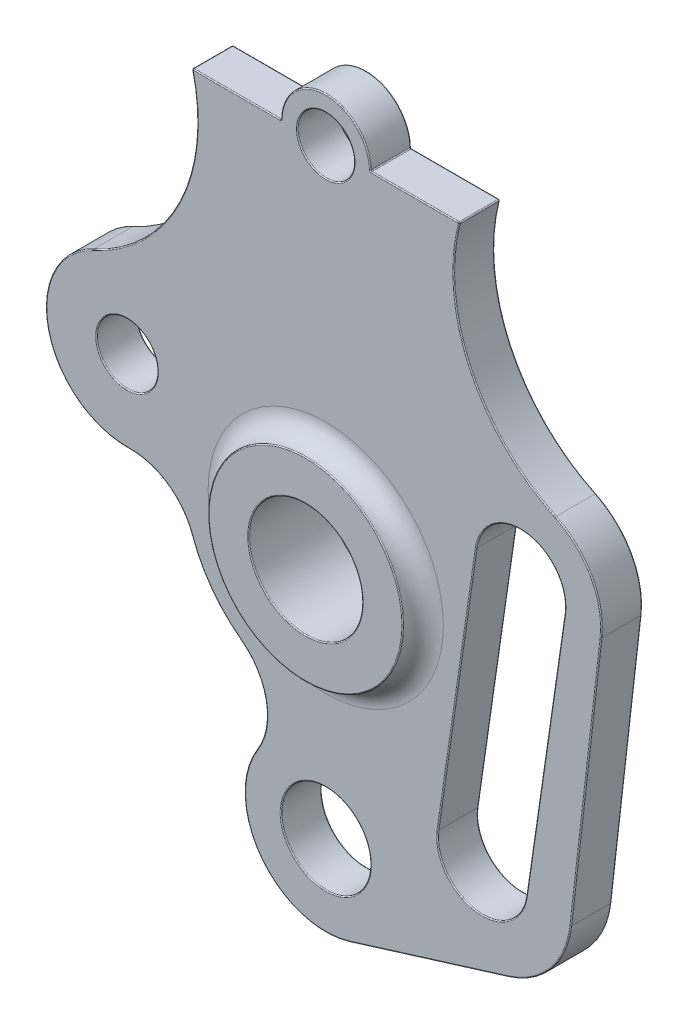
SolidWorks part; units mm, degrees
note: The reader was unsure of these and kept them because the rebuilt part matched: shared geometry of "Sketch1<5>".
ref_plane "Front Plane" through (0, 0, 0) normal (0, 0, 1) x (1, 0, 0)
ref_plane "Top Plane" through (0, 0, 0) normal (0, 1, 0) x (1, 0, 0)
ref_plane "Right Plane" through (0, 0, 0) normal (1, 0, 0) x (0, 0, -1)
sketch "Sketch1" plane through (0, 0, 0) normal (0, 0, 1) x (1, 0, 0)
  line L0 (0, 0) -> (0, 24886.7908) construction
  line L1 (0, 0) -> (24886.7908, 0) construction
  line L2 (48, 19) -> (38.5673, -45.9627) construction
  line L3 (58.8858, 17.4193) -> (49.4531, -47.5433)
  line L4 (37.1142, 20.5807) -> (27.6814, -44.382)
  line L5 (0, 0) -> (38.5673, -45.9627) construction
  line L6 (-33, 88) -> (-11, 88)
  line L7 (5.9165, -79.1049) -> (45.0754, -66.978)
  line L8 (60.4251, -48.4592) -> (67.8708, 16.7304)
  line L9 (33, 88) -> (11, 88)
  circle A0 centre (0, 0) radius 14
  circle A1 centre (0, 88) radius 7
  circle A2 centre (0, -60) radius 11
  arc A3 (11, 88) -> (-11, 88) centre (0, 88) ccw
  circle A4 centre (-49, 19) radius 7.5
  arc A5 (-57.3283, 37.1835) -> (-48.493, -0.9936) centre (-49, 19) ccw
  arc A6 (58.8858, 17.4193) -> (37.1142, 20.5807) centre (48, 19) ccw
  arc A7 (27.6814, -44.382) -> (49.4531, -47.5433) centre (38.5673, -45.9627) ccw
  arc A8 (-16.9443, -49.375) -> (5.9165, -79.1049) centre (0, -60) ccw
  arc A9 (45.0754, -66.978) -> (60.4251, -48.4592) centre (38.5673, -45.9627) ccw
  arc A10 (-33, 88) -> (-57.3283, 37.1835) centre (-75.6507, 77.1871) cw
  arc A11 (-33.0011, -11.6587) -> (-20.9312, -28.0515) centre (0, 0) ccw
  arc A12 (-48.493, -0.9936) -> (-33.0011, -11.6587) centre (-48.0874, -16.9884) cw
  arc A13 (-20.9312, -28.0515) -> (-16.9443, -49.375) centre (-30.4997, -40.875) cw
  arc A14 (34.714, 4.0507) -> (34.7706, 4.0006) centre (48, 19) ccw
  arc A15 (33, 88) -> (56.6071, 37.0532) centre (75.5428, 76.7702) ccw
  arc A16 (67.8708, 16.7304) -> (56.6071, 37.0532) centre (48, 19) ccw
  arc A17 (34.7706, 4.0006) -> (34.7419, 4.2429) centre (0, 0) ccw
  point P17 (43.2836, -13.4813)
  point P42 (41.1561, -49.0479)
  point P43 (0, 99)
  dimension "D1" = 28
  dimension "D2" = 14
  dimension "D3" = 22
  dimension "D5" = 49
  dimension "D8" = 11
  dimension "D12" = 22
  dimension "D13" = 70
  dimension "D14" = 16
  dimension "D16" = 16
  dimension "D17" = 44
  dimension "D18" = 40
  dimension "D15" = 44
  dimension "D19" = 44
  dimension "D20" = 22
  dimension "D21" = 40
  dimension "D22" = 15
  dimension "D23" = 40
  dimension "D4" = 88
  dimension "D6" = 69
  dimension "D7" = 60
  dimension "D9" = 40
  dimension "D10" = 48
  dimension "D11" = 19
  dimension "D24" = 60
extrude "Extrude-Thin1" add sketch "Sketch1" along normal mid plane 20 thin contours A0
extrude "Boss-Extrude2" add sketch "Sketch1<5>" along normal mid plane 10 contours L8 A16 A15 L9 A3 L6 A10 A5 A12 A11 A13 A8 L7 A9 A0 A1 A2 A4 A7 L4 A6 L3
sketch "Sketch1<5>" plane through (0, 0, 0) normal (0, 0, 1) x (1, 0, 0) same geometry as "Sketch1"
fillet "Fillet1" radius 5 2 edges at (24, 0, -5) (24, 0, 5)
fillet "Fillet2" radius 0.25 50 edges at (54.1695, -15.062, -5) (-39.0145, -3.8095, -5) (-28.1843, -20.752, -5) (-14.7723, -37.9344, -5) (-15.8546, -72.1914, -5) (25.4959, -73.0414, -5) (7, 88, -5) (11, -60, -5) (-41.5, 19, -5) (36.9866, -56.8485, -5) (32.3978, -11.9007, -5) (49.5807, 29.8858, -5) (64.148, -15.8644, -5) (65.4929, 28.6953, -5) (35.6204, 58.2714, -5) (22, 88, -5) (0, 99, -5) (-22, 88, -5) (-35.9643, 58.1873, -5) (-68.485, 14.4906, -5) (55.5052, -60.0021, -5) (7, 88, 5) (11, -60, 5) (-41.5, 19, 5) (36.9866, -56.8485, 5) (32.3978, -11.9007, 5) (49.5807, 29.8858, 5) (54.1695, -15.062, 5) (64.148, -15.8644, 5) (65.4929, 28.6953, 5) (35.6204, 58.2714, 5) (22, 88, 5) (0, 99, 5) (-22, 88, 5) (-35.9643, 58.1873, 5) (-68.485, 14.4906, 5) (-39.0145, -3.8095, 5) (-28.1843, -20.752, 5) (-14.7723, -37.9344, 5) (-15.8546, -72.1914, 5) (25.4959, -73.0414, 5) (55.5052, -60.0021, 5) (-33, 88, 0) (-11, 88, 0) (11, 88, 0) (33, 88, 0) (14, 0, -10) (14, 0, 10) (24, 0, -10) (24, 0, 10)
